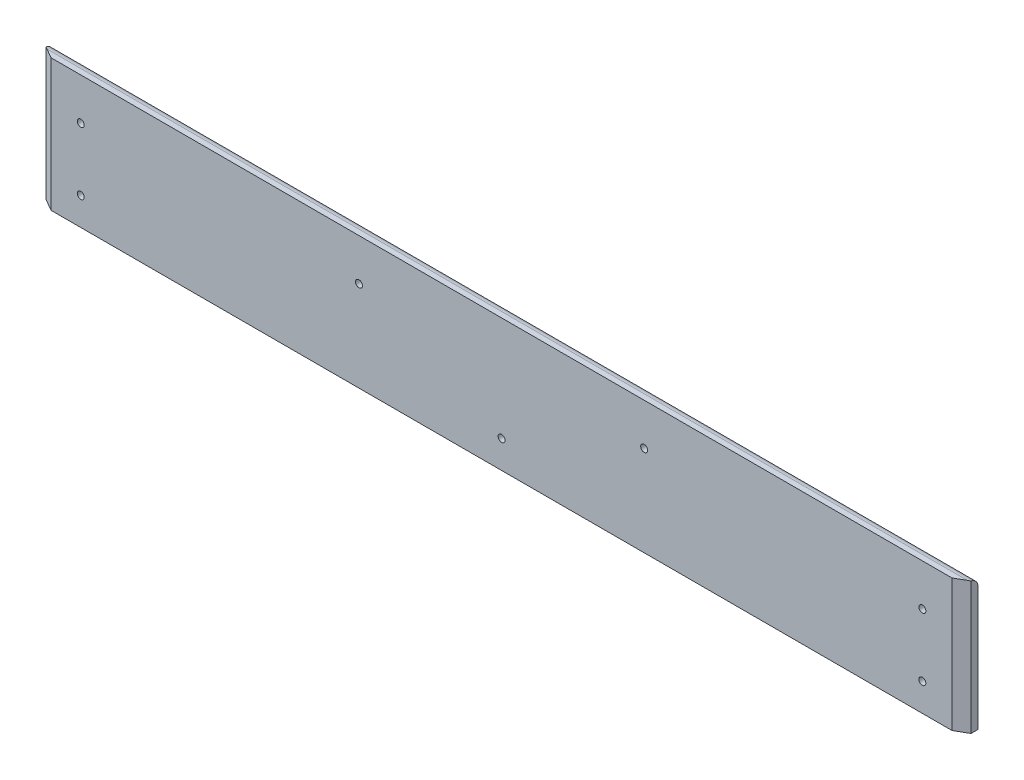
SolidWorks part; units mm, degrees
material "Холодостойкий пластик  -60 гр."
ref_plane "Спереди" through (0, 0, 0) normal (0, 0, 1) x (1, 0, 0)
ref_plane "Сверху" through (0, 0, 0) normal (0, 1, 0) x (1, 0, 0)
ref_plane "Справа" through (0, 0, 0) normal (1, 0, 0) x (0, 0, -1)
sketch "Эскиз1" plane through (0, 0, 0) normal (0, 0, 1) x (1, 0, 0)
  line L1 (-332.5, -47.5) -> (332.5, -47.5)
  line L2 (-332.5, -47.5) -> (-332.5, 47.5)
  line L3 (-332.5, 47.5) -> (332.5, 47.5)
  line L4 (332.5, -47.5) -> (332.5, 47.5)
  line L5 (0, 47.5) -> (0, -47.5) construction
  line L6 (-332.5, 0) -> (332.5, 0) construction
  point P0 (0, 0)
  dimension "D1" = 665
  dimension "D2" = 95
extrude "Бобышка-Вытянуть1" add sketch "Эскиз1" along normal mid plane 10
fillet "Скругление1" radius 6 1 edges at (0, 47.5, -5)
chamfer "Фаска1" distance 5 angle 60 2 edges at (332.5, 0, 5) (-332.5, 0, 5) first distance on face at (332.5, 8.5485, -0.0485) first distance on face at (-332.5, 8.5485, -0.0485)
sketch "Эскиз3" plane through (0, 0, 5) normal (0, 0, 1) x (1, 0, 0)
  line L0 (-323.8397, -47.5) -> (323.8397, -47.5) construction
  line L1 (-332.5, -47.5) -> (-332.5, 47.4161) construction
  line L2 (332.5, 47.4161) -> (332.5, -47.5) construction
  line L3 (0, -50) -> (0, 50) construction
  circle A0 centre (-302.5, -27.5) radius 2.5
  circle A1 centre (0, -27.5) radius 2.5
  circle A2 centre (302.5, -27.5) radius 2.5
  circle A3 centre (-302.5, 17.5) radius 2.5
  circle A4 centre (302.5, 17.5) radius 2.5
  circle A5 centre (-102.5, 17.5) radius 2.5
  circle A6 centre (102.5, 17.5) radius 2.5
  dimension "D1" = 5
  dimension "D2" = 20
  dimension "D3" = 30
  dimension "D4" = 30
  dimension "D5" = 45
  dimension "D6" = 200
  dimension "D7" = 200
extrude "Вырез-Вытянуть1" cut sketch "Эскиз3" against normal through all
chamfer "Фаска2" distance 2 angle 45 7 edges at (-300, -27.5, -5) (-300, 17.5, -5) (-100, 17.5, -5) (2.5, -27.5, -5) (105, 17.5, -5) (305, -27.5, -5) (305, 17.5, -5)
